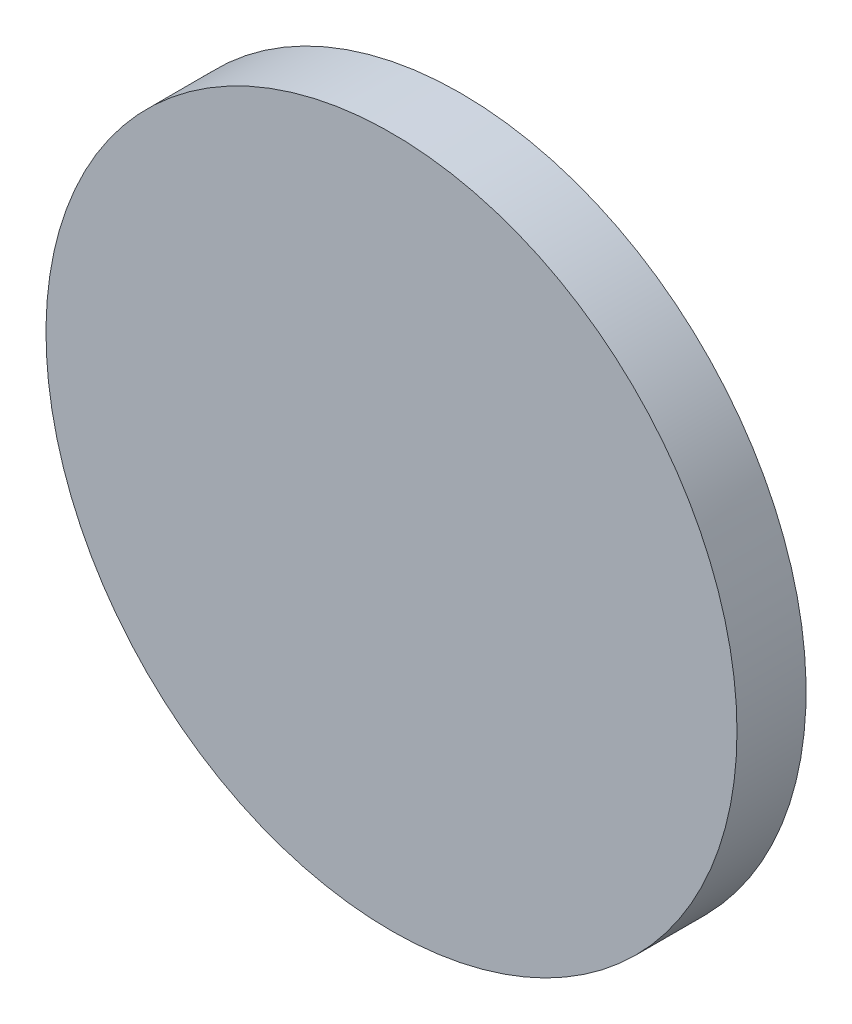
SolidWorks part; units mm, degrees
ref_plane "前视基准面" through (0, 0, 0) normal (0, 0, 1) x (1, 0, 0)
ref_plane "上视基准面" through (0, 0, 0) normal (0, 1, 0) x (1, 0, 0)
ref_plane "右视基准面" through (0, 0, 0) normal (1, 0, 0) x (0, 0, -1)
other "Configuration Table"
sketch "草图1" plane through (0, 0, 0) normal (0, 0, 1) x (1, 0, 0)
  line L0 (-4.9697, -5.3371) -> (15.3903, -5.3371) construction
  line L1 (-1.7897, -9.462) -> (12.2103, -9.462) construction
  line L2 (5.2103, 9.538) -> (5.2103, -5.6737) construction
  line L3 (5.2103, -5.6737) -> (5.2103, -9.462) construction
  line L4 (-20.5262, 27.563) -> (29.3458, 27.563) construction
  arc A1 (15.3903, -5.3371) -> (-4.9697, -5.3371) centre (5.2103, 9.538) ccw construction
  circle A2 centre (5.2103, 9.538) radius 18.025 construction
  circle A3 centre (5.2103, 9.538) radius 20 construction
  spline S0 degree 2 poles (-4.9697, -5.3371) (-1.8954, -6.8939) (-1.7897, -9.462) knots 0 0 0 0.933514 0.933514 0.933514 construction
  spline S1 degree 2 poles (15.3903, -5.3371) (12.316, -6.8939) (12.2103, -9.462) knots 0 0 0 0.933514 0.933514 0.933514 construction
  point P7 (5.2103, -9.462)
  dimension "D1" = 20.36
  dimension "D2" = 36.05
  dimension "D6" = 40
  dimension "D3" = 19
  dimension "D4" = 14
  dimension "D5" = 37.025
sketch "草图2" plane through (0, 0, 0) normal (0, 0, 1) x (1, 0, 0)
  circle A0 centre (5.2103, 9.538) radius 20
  circle A1 centre (5.2103, 9.538) radius 20 construction
extrude "凸台-拉伸1" add sketch "草图2" along normal blind 4
sketch "草图3" plane through (0, 0, 0) normal (0, 0, 1) x (1, 0, 0)
  arc A1 (-2.2893, -9.4826) -> (12.7099, -9.4826) centre (5.2103, 9.538) ccw
  arc A2 (15.645, -5.7687) -> (-5.2244, -5.7687) centre (5.2103, 9.538) ccw
  arc A3 (15.645, -5.7687) -> (-5.2244, -5.7687) centre (5.2103, 9.538) ccw
  spline S0 degree 3 poles (1417.1009, -4798.1847) (368.2629, -190.5241) (2.5533, -36.5813) (13.0442, -8.0705) (13.2228, -7.7504) (36.9463, 22.8452) (653.5299, -69.7294) (4370.8812, -2442.513) knots -20.612326 -20.612326 -20.612326 -20.612326 0.25 0.25 0.5 0.5 25.135238 25.135238 25.135238 25.135238 only from (12.7099, -9.4826) to (15.645, -5.7687)
  spline S1 degree 3 poles (-4360.5949, -2442.5987) (-643.1242, -69.7316) (-26.526, 22.8456) (-2.8022, -7.7504) (-2.6237, -8.0705) (7.8672, -36.581) (-357.8345, -190.5208) (-1406.6465, -4798.0361) knots -24.135535 -24.135535 -24.135535 -24.135535 0.5 0.5 0.75 0.75 21.612102 21.612102 21.612102 21.612102 only from (-5.2244, -5.7687) to (-2.2893, -9.4826)
  spline S2 degree 3 poles (12.7099, -9.4826) (12.7255, -9.1014) (12.7958, -8.7458) (13.0442, -8.0705) (13.2228, -7.7504) (13.9377, -6.8283) (14.6587, -6.2641) (15.645, -5.7687) knots 0 0 0 0 0.25 0.25 0.5 0.5 1 1 1 1
  spline S3 degree 3 poles (-5.2244, -5.7687) (-4.2382, -6.2641) (-3.5172, -6.8283) (-2.8022, -7.7504) (-2.6237, -8.0705) (-2.3752, -8.7458) (-2.305, -9.1014) (-2.2893, -9.4826) knots 0 0 0 0 0.5 0.5 0.75 0.75 1 1 1 1
  dimension "D1" = 0.5
extrude "切除-拉伸1" cut sketch "草图3" along normal blind 3
